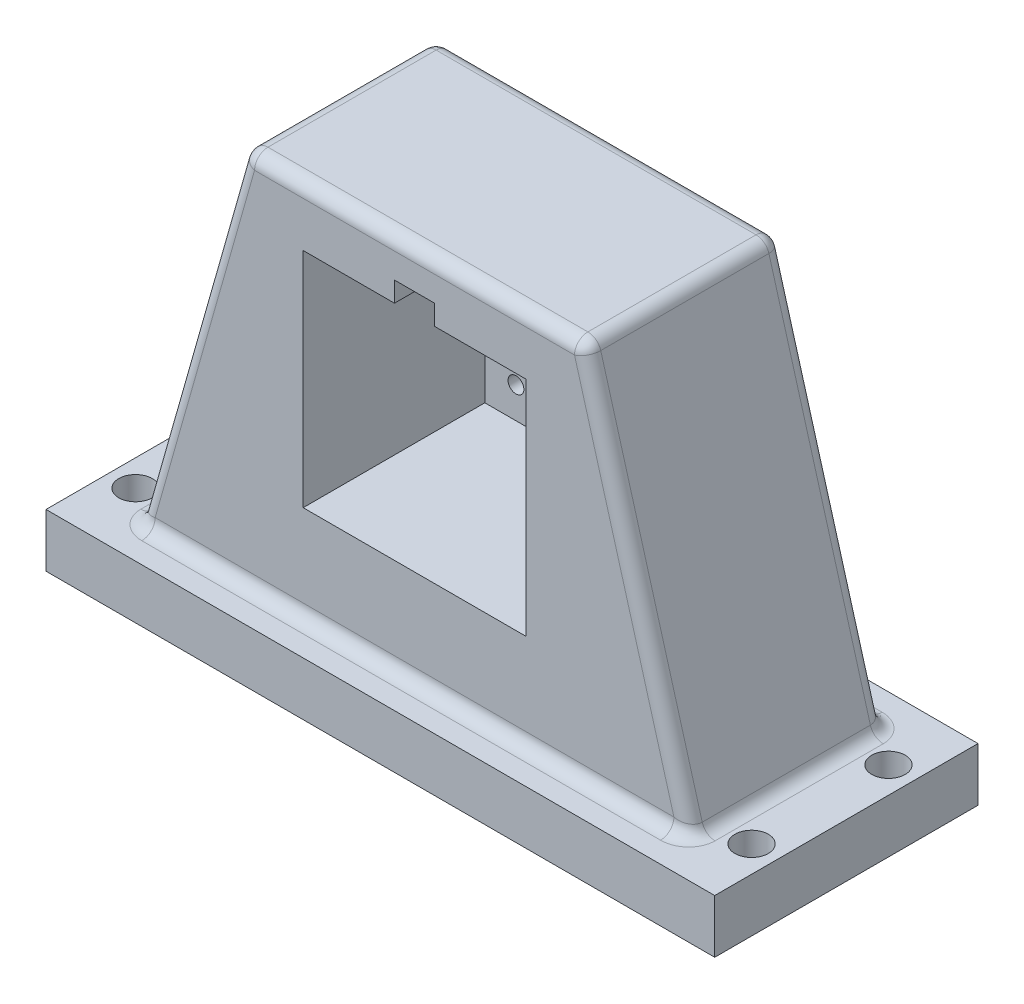
SolidWorks part; units mm, degrees
ref_plane "Front Plane" through (0, 0, 0) normal (0, 0, 1) x (1, 0, 0)
ref_plane "Top Plane" through (0, 0, 0) normal (0, 1, 0) x (1, 0, 0)
ref_plane "Right Plane" through (0, 0, 0) normal (1, 0, 0) x (0, 0, -1)
sketch "Sketch1" plane through (0, 0, 0) normal (0, 0, 1) x (1, 0, 0)
  line L1 (63.5, 5.08) -> (-63.5, 5.08)
  line L2 (63.5, 5.08) -> (63.5, -5.08)
  line L3 (63.5, -5.08) -> (-63.5, -5.08)
  line L4 (-63.5, 5.08) -> (-63.5, -5.08)
  line L5 (63.5, 5.08) -> (-63.5, -5.08) construction
  line L6 (63.5, -5.08) -> (-63.5, 5.08) construction
  point P0 (0, 0)
  dimension "D1" = 10.16
  dimension "D2" = 127
extrude "Boss-Extrude1" add sketch "Sketch1" along normal blind 50
sketch "Sketch2" plane through (0, 5.08, 0) normal (0, 1, 0) x (1, 0, 0)
  line L1 (32.3, -43.508) -> (-32.3, -43.508)
  line L2 (32.3, -43.508) -> (32.3, -6.492)
  line L3 (32.3, -6.492) -> (-32.3, -6.492)
  line L4 (-32.3, -43.508) -> (-32.3, -6.492)
  line L5 (32.3, -43.508) -> (-32.3, -6.492) construction
  line L6 (32.3, -6.492) -> (-32.3, -43.508) construction
  line L7 (-63.5, -50) -> (-63.5, 0) construction
  point P0 (0, -25)
  point P10 (-63.5, -25)
  dimension "D1" = 37.016
  dimension "D2" = 64.6
extrude "Boss-Extrude2" add sketch "Sketch2" along normal blind 71.628
sketch "Sketch3" plane through (0, 0, 43.508) normal (0, 0, 1) x (1, 0, 0)
  line L5 (21.15, 65.6) -> (-21.15, 65.6)
  line L6 (21.15, 65.6) -> (21.15, 23.3)
  line L7 (21.15, 23.3) -> (-21.15, 23.3)
  line L8 (-21.15, 65.6) -> (-21.15, 23.3)
  line L9 (21.15, 65.6) -> (-21.15, 23.3) construction
  line L10 (21.15, 23.3) -> (-21.15, 65.6) construction
  line L11 (-63.5, -5.08) -> (63.5, -5.08) construction
  point P0 (0, 44.45)
  dimension "D1" = 42.3
  dimension "D2" = 49.53
extrude "Cut-Extrude1" cut sketch "Sketch3" against normal blind 34.5
sketch "Sketch4" plane through (0, 0, 9.008) normal (0, 0, 1) x (1, 0, 0)
  line L0 (21.15, 65.6) -> (-21.15, 65.6) construction
  line L1 (-21.15, 65.6) -> (-21.15, 23.3) construction
  circle A0 centre (0, 44.45) radius 11
  point P5 (0, 65.6)
  point P9 (-21.15, 44.45)
  dimension "D1" = 22
extrude "Cut-Extrude2" cut sketch "Sketch4" against normal through all
sketch "Sketch5" plane through (0, 5.08, 0) normal (0, 1, 0) x (1, 0, 0)
  line L0 (-63.5, -50) -> (-63.5, 0) construction
  line L1 (63.5, -50) -> (63.5, 0) construction
  line L2 (63.5, 0) -> (-63.5, 0) construction
  line L3 (63.5, -50) -> (-63.5, -50) construction
  circle A0 centre (58.5, -12) radius 3.175
  circle A1 centre (58.5, -38) radius 3.175
  circle A2 centre (-58.5, -12) radius 3.175
  circle A3 centre (-58.5, -38) radius 3.175
  dimension "D1" = 6.35
  dimension "D2" = 5
  dimension "D3" = 5
  dimension "D4" = 12
  dimension "D5" = 12
extrude "Cut-Extrude3" cut sketch "Sketch5" against normal blind 34.5
sketch "Sketch8" plane through (0, 0, 43.508) normal (0, 0, 1) x (1, 0, 0)
  line L0 (-32.3, 76.708) -> (-32.3, 5.08)
  line L1 (-32.3, 5.08) -> (-52.62, 5.08)
  line L2 (63.5, 5.08) -> (-63.5, 5.08) construction
  line L3 (-52.62, 5.08) -> (-32.3, 76.708)
  line L4 (0, 0) -> (0, 76.708) construction
  line L5 (-32.3, 76.708) -> (32.3, 76.708) construction
  line L6 (32.3, 5.08) -> (52.62, 5.08)
  line L7 (32.3, 76.708) -> (32.3, 5.08)
  line L8 (52.62, 5.08) -> (32.3, 76.708)
  dimension "D1" = 20.32
extrude "Boss-Extrude5" add sketch "Sketch8" against normal up to vertex (37.016 mm away) up to point (32.3, 5.08, 6.492)
sketch "Sketch9" plane through (0, 0, 6.492) normal (0, 0, -1) x (-1, 0, 0)
  line L1 (15.24, 29.21) -> (-15.24, 29.21)
  line L2 (15.24, 29.21) -> (15.24, 59.69)
  line L3 (15.24, 59.69) -> (-15.24, 59.69)
  line L4 (-15.24, 29.21) -> (-15.24, 59.69)
  line L5 (15.24, 29.21) -> (-15.24, 59.69) construction
  line L6 (15.24, 59.69) -> (-15.24, 29.21) construction
  circle A0 centre (-15.24, 59.69) radius 1.5
  circle A1 centre (15.24, 59.69) radius 1.5
  circle A2 centre (-15.24, 29.21) radius 1.5
  circle A3 centre (15.24, 29.21) radius 1.5
  point P0 (0, 44.45)
  dimension "D1" = 3
  dimension "D2" = 30.48
extrude "Cut-Extrude4" cut sketch "Sketch9" against normal up to next contours L3 A0 L4 | L4 A0 L3 | L2 A1 L3 | L3 A1 L2 | L1 A3 L2 | L2 A3 L1 | L1 A2 L4 | L4 A2 L1 region at (15.4522, 28.9978, 6.492) region at (14.6034, 29.8466, 6.492) region at (-14.6034, 29.8466, 6.492) region at (-15.4522, 28.9978, 6.492) region at (15.4522, 59.9022, 6.492) region at (14.6034, 59.0534, 6.492) region at (-14.6034, 59.0534, 6.492) region at (-15.4522, 59.9022, 6.492)
sketch "Sketch10" plane through (0, 0, 43.508) normal (0, 0, 1) x (1, 0, 0)
  line L0 (21.15, 65.6) -> (-21.15, 65.6) construction
  line L1 (-3.81, 69.41) -> (3.81, 69.41)
  line L2 (-3.81, 69.41) -> (-3.81, 65.6)
  line L3 (-3.81, 65.6) -> (3.81, 65.6)
  line L4 (3.81, 69.41) -> (3.81, 65.6)
  line L5 (-3.81, 69.41) -> (3.81, 65.6) construction
  line L6 (-3.81, 65.6) -> (3.81, 69.41) construction
  point P0 (0, 67.505)
  point P8 (0, 65.6)
  dimension "D1" = 3.81
  dimension "D2" = 7.62
extrude "Cut-Extrude5" cut sketch "Sketch10" against normal blind 7.62
fillet "Fillet1" radius 2.54 12 edges at (0, 5.08, 43.508) (52.62, 5.08, 25) (-52.62, 5.08, 25) (0, 5.08, 6.492) (42.46, 40.894, 43.508) (42.46, 40.894, 6.492) (32.3, 76.708, 25) (0, 76.708, 43.508) (-32.3, 76.708, 25) (-42.46, 40.894, 43.508) (-42.46, 40.894, 6.492) (0, 76.708, 6.492)
